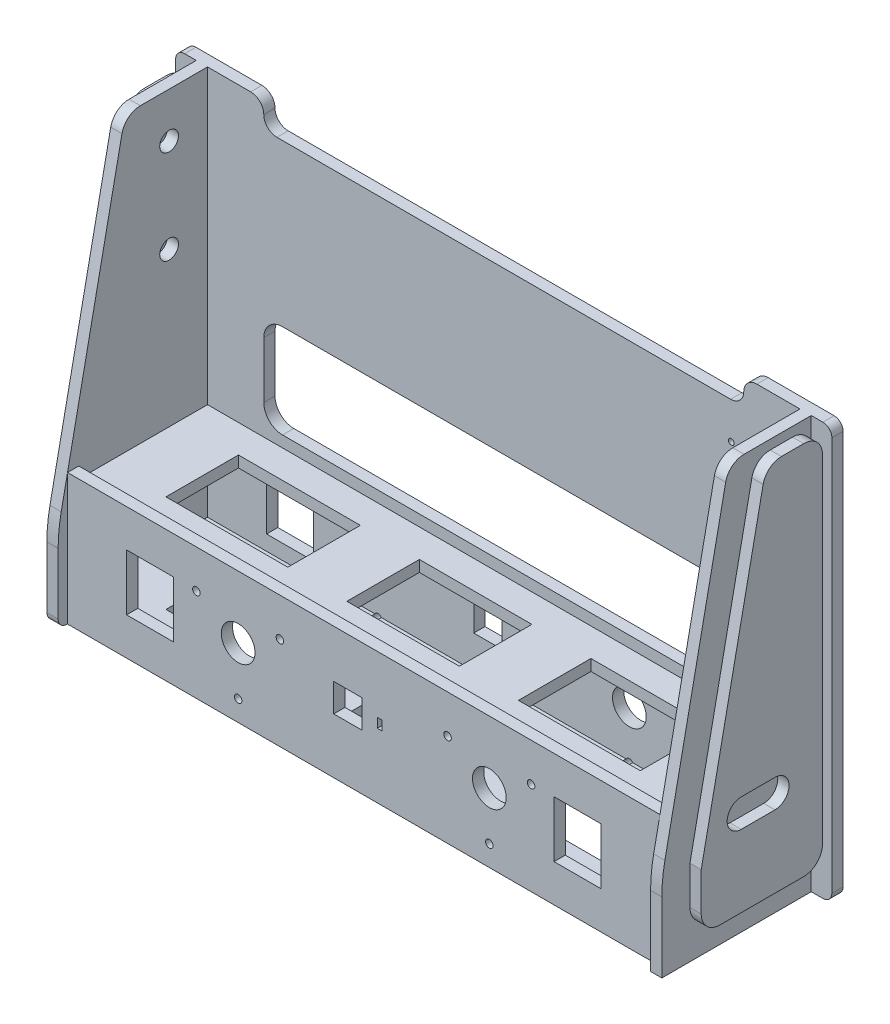
SolidWorks part; units mm, degrees
material "Birch plywood FK"
ref_plane "Спереди" through (0, 0, 0) normal (0, 0, 1) x (1, 0, 0)
ref_plane "Сверху" through (0, 0, 0) normal (0, 1, 0) x (1, 0, 0)
ref_plane "Справа" through (0, 0, 0) normal (1, 0, 0) x (0, 0, -1)
sketch "Эскиз1" plane through (0, 0, 0) normal (1, 0, 0) x (0, 0, -1)
  line L0 (0, 220) -> (0, 0)
  line L1 (0, 0) -> (-95, 0)
  line L2 (-95, 0) -> (-50, 220)
  line L3 (-50, 220) -> (0, 220)
  dimension "D1" = 220
  dimension "D2" = 95
  dimension "D3" = 50
extrude "Бобышка-Вытянуть1" add sketch "Эскиз1" along normal blind 340
sketch "Эскиз2" plane through (0, 220, 0) normal (0, 1, 0) x (1, 0, 0)
  line L0 (170, -95) -> (170, 0) construction
  line L1 (340, -95) -> (0, -95) construction
  line L2 (340, 0) -> (0, 0) construction
  line L3 (340, -50) -> (340, -95) construction
  line L4 (12, -95) -> (328, -95)
  line L5 (12, -95) -> (12, -6)
  line L6 (12, -6) -> (328, -6)
  line L7 (328, -95) -> (328, -6)
  line L8 (12, -95) -> (328, -6) construction
  line L9 (12, -6) -> (328, -95) construction
  point P6 (170, -50.5)
  dimension "D1" = 12
  dimension "D2" = 6
extrude "Вырез-Вытянуть1" cut sketch "Эскиз2" against normal offset from surface (150 mm away) 70 up to face at (170, 0, 47.5)
sketch "Эскиз3" plane through (0, 70, 0) normal (0, 1, 0) x (1, 0, 0)
  line L0 (340, -95) -> (0, -95) construction
  line L1 (12, -80.6818) -> (328, -80.6818)
  line L2 (12, -80.6818) -> (12, -95)
  line L3 (12, -95) -> (328, -95)
  line L4 (328, -80.6818) -> (328, -95)
extrude "Вырез-Вытянуть2" cut sketch "Эскиз3" against normal through all
sketch "Эскиз4" plane through (0, 0, 80.6818) normal (0, 0, 1) x (1, 0, 0)
  line L0 (170, 70) -> (170, 0) construction
  line L1 (12, 70) -> (328, 70) construction
  line L2 (328, 0) -> (12, 0) construction
  line L3 (12, 0) -> (12, 70) construction
  line L4 (328, 12) -> (12, 12)
  line L5 (328, 12) -> (328, 58)
  line L6 (328, 58) -> (12, 58)
  line L7 (12, 12) -> (12, 58)
  line L8 (328, 12) -> (12, 58) construction
  line L9 (328, 58) -> (12, 12) construction
  line L10 (12, 70) -> (328, 70) construction
  line L12 (328, 64) -> (12, 64)
  line L13 (328, 64) -> (328, 70)
  line L14 (328, 70) -> (12, 70)
  line L15 (12, 64) -> (12, 70)
  line L16 (328, 64) -> (12, 70) construction
  line L17 (328, 70) -> (12, 64) construction
  line L18 (328, 6) -> (12, 6)
  line L19 (328, 6) -> (328, 0)
  line L20 (328, 0) -> (12, 0)
  line L21 (12, 6) -> (12, 0)
  line L22 (328, 6) -> (12, 0) construction
  line L23 (328, 0) -> (12, 6) construction
  point P6 (170, 35)
  point P15 (170, 67)
  point P21 (170, 3)
  dimension "D1" = 12
  dimension "D2" = 6
extrude "Вырез-Вытянуть3" cut sketch "Эскиз4" against normal offset from surface (68.6818 mm away) 6 from offset 6 up to face at (170, 110, 0) offset against normal yes
sketch "Эскиз5" plane through (0, 0, 6) normal (0, 0, 1) x (1, 0, 0)
  line L0 (170, 220) -> (170, 70) construction
  line L1 (328, 220) -> (12, 220) construction
  line L2 (12, 70) -> (328, 70) construction
  line L3 (12, 64) -> (12, 220) construction
  line L4 (298, 70) -> (42, 70)
  line L5 (298, 70) -> (298, 120)
  line L6 (298, 120) -> (42, 120)
  line L7 (42, 70) -> (42, 120)
  line L8 (298, 70) -> (42, 120) construction
  line L9 (298, 120) -> (42, 70) construction
  point P6 (170, 95)
  dimension "D1" = 30
  dimension "D2" = 50
extrude "Вырез-Вытянуть4" cut sketch "Эскиз5" against normal through all
sketch "Эскиз6" plane through (0, 70, 0) normal (0, 1, 0) x (1, 0, 0)
  line L0 (170, 0) -> (170, -80.6818) construction
  line L1 (42, 0) -> (298, 0) construction
  line L2 (12, -80.6818) -> (328, -80.6818) construction
  line L3 (12, -6) -> (42, -6) construction
  line L4 (140, -40.3409) -> (12, -40.3409) construction
  line L5 (12, -6) -> (12, -74.6818) construction
  line L6 (200, -59.6818) -> (140, -59.6818)
  line L7 (200, -59.6818) -> (200, -21)
  line L8 (200, -21) -> (140, -21)
  line L9 (140, -59.6818) -> (140, -21)
  line L10 (200, -59.6818) -> (140, -21) construction
  line L11 (200, -21) -> (140, -59.6818) construction
  line L13 (108.5, -21) -> (43.5, -21)
  line L14 (328, -6) -> (328, -74.6818) construction
  line L15 (328, -40.3409) -> (200, -40.3409) construction
  line L16 (108.5, -21) -> (108.5, -59.6818)
  line L17 (108.5, -59.6818) -> (43.5, -59.6818)
  line L19 (43.5, -21) -> (43.5, -59.6818)
  line L20 (108.5, -21) -> (43.5, -59.6818) construction
  line L21 (108.5, -59.6818) -> (43.5, -21) construction
  line L22 (296.5, -21) -> (231.5, -21)
  line L23 (296.5, -21) -> (296.5, -59.6818)
  line L24 (296.5, -59.6818) -> (231.5, -59.6818)
  line L25 (231.5, -21) -> (231.5, -59.6818)
  line L26 (296.5, -21) -> (231.5, -59.6818) construction
  line L27 (296.5, -59.6818) -> (231.5, -21) construction
  point P6 (170, -40.3409)
  point P18 (76, -40.3409)
  point P28 (264, -40.3409)
  dimension "D1" = 15
  dimension "D2" = 60
  dimension "D3" = 65
extrude "Вырез-Вытянуть5" cut sketch "Эскиз6" against normal through all
sketch "Эскиз8" plane through (0, 0, 0) normal (-1, 0, 0) x (0, 0, 1)
  line L0 (95, 0) -> (0, 0) construction
  line L1 (85.6818, 70) -> (95, 70)
  line L2 (85.6818, 70) -> (85.6818, 0)
  line L3 (85.6818, 0) -> (95, 0)
  line L4 (95, 70) -> (95, 0)
  line L5 (80.6818, 0) -> (80.6818, 70) construction
  line L6 (80.6818, 70) -> (74.6818, 70) construction
  dimension "D1" = 5
extrude "Вырез-Вытянуть7" cut sketch "Эскиз8" against normal through all
sketch "Эскиз10" plane through (0, 220, 0) normal (0, 1, 0) x (1, 0, 0)
  line L0 (328, -6) -> (12, -6) construction
  line L1 (0, 0) -> (-5, 0)
  line L2 (0, 0) -> (0, -6)
  line L3 (0, -6) -> (-5, -6)
  line L4 (-5, 0) -> (-5, -6)
  line L5 (340, 0) -> (345, 0)
  line L6 (340, 0) -> (340, -6)
  line L7 (340, -6) -> (345, -6)
  line L8 (345, 0) -> (345, -6)
  dimension "D1" = 5
  dimension "D2" = 5
extrude "Бобышка-Вытянуть3" add sketch "Эскиз10" against normal up to surface (220 mm away) up to face at (170, 0, 63.0114)
sketch "Эскиз12" plane through (0, 0, 0) normal (-1, 0, 0) x (0, 0, 1)
  circle A0 centre (26.5, 196) radius 5
  circle A1 centre (26.5, 146) radius 5
  dimension "D1" = 10
extrude "Вырез-Вытянуть9" cut sketch "Эскиз12" against normal offset from surface (328 mm away) 6 from offset 6 up to face at (340, 75.1111, 50.2409) offset against normal yes
sketch "Эскиз13" plane through (0, 0, 6) normal (0, 0, 1) x (1, 0, 0)
  line L0 (334, 191) -> (345, 191) construction
  line L1 (345, 0) -> (345, 220) construction
  line L2 (306.85, 191) -> (306.85, 151) construction
  line L3 (334, 151) -> (345, 151) construction
  line L4 (306.85, 171) -> (345, 171) construction
  line L5 (340, 220) -> (340, 45.5556) construction
  circle A0 centre (306.85, 171) radius 16.4
  circle A2 centre (291.35, 186.5) radius 1.5
  circle A3 centre (322.35, 186.5) radius 1.5
  circle A4 centre (322.35, 155.5) radius 1.5
  circle A5 centre (291.35, 155.5) radius 1.5
  circle A6 centre (306.85, 171) radius 16.4 construction
  point P0 (306.85, 171)
  point P2 (0, 0)
  dimension "D1" = 3
  dimension "D2" = 33.15
extrude "Вырез-Вытянуть10" cut sketch "Эскиз13" against normal through all
fillet "Скругление2" radius 10 2 edges at (6, 220, 50) (334, 220, 50)
fillet "Скругление4" radius 80 2 edges at (334, 45.5556, 85.6818) (6, 45.5556, 85.6818)
sketch "Эскиз16" plane through (0, 0, 80.6818) normal (0, 0, 1) x (1, 0, 0)
  circle A0 centre (103, 36.7238) radius 9
  circle A1 centre (237, 36.7238) radius 9
  dimension "D1" = 18
extrude "Вырез-Вытянуть12" cut sketch "Эскиз16" against normal through all
sketch "Эскиз19" plane through (0, 0, 80.6818) normal (0, 0, 1) x (1, 0, 0)
  line L0 (161.5, 37) -> (178.5, 37) construction
  line L1 (169, 29.5) -> (154, 29.5)
  line L2 (169, 29.5) -> (169, 44.5)
  line L3 (169, 44.5) -> (154, 44.5)
  line L4 (154, 29.5) -> (154, 44.5)
  line L5 (169, 29.5) -> (154, 44.5) construction
  line L6 (169, 44.5) -> (154, 29.5) construction
  line L7 (179.75, 34.5) -> (177.25, 34.5)
  line L8 (179.75, 34.5) -> (179.75, 39.5)
  line L9 (179.75, 39.5) -> (177.25, 39.5)
  line L10 (177.25, 34.5) -> (177.25, 39.5)
  line L11 (179.75, 34.5) -> (177.25, 39.5) construction
  line L12 (179.75, 39.5) -> (177.25, 34.5) construction
  line L13 (170, 37) -> (170, -29) construction
  line L14 (153.0926, -29) -> (186.9074, -29) construction
  line L15 (60, 24.5) -> (280, 24.5) construction
  circle A0 centre (125.2775, 49.5857) radius 2
  circle A1 centre (80.7225, 49.5857) radius 2
  circle A2 centre (103, 11) radius 2
  circle A3 centre (214.7225, 49.5857) radius 2
  circle A4 centre (259.2775, 49.5857) radius 2
  circle A5 centre (237, 11) radius 2
  point P0 (161.5, 37)
  point P5 (178.5, 37)
  dimension "D7" = 4
  dimension "D1" = 5
  dimension "D2" = 2.5
  dimension "D3" = 12.5
  dimension "D4" = 17
  dimension "D5" = 15
  dimension "D6" = 15
extrude "Вырез-Вытянуть15" cut sketch "Эскиз19" against normal through all
fillet "Скругление5" radius 4.8 5 edges at (-5, 220, 3) (6, 0, 85.6818) (-5, 0, 3) (345, 0, 3) (345, 220, 3)
fillet "Скругление6" radius 10 4 edges at (298, 70, 3) (298, 120, 3) (42, 70, 3) (42, 120, 3)
sketch "Эскиз20" plane through (0, 0, 6) normal (0, 0, 1) x (1, 0, 0)
  line L0 (319.5142, 124.6) -> (309.5142, 124.6) construction
  line L1 (319.5142, 124.1) -> (309.5142, 124.1)
  line L2 (319.5142, 125.1) -> (309.5142, 125.1)
  line L3 (319.5142, 115.1) -> (309.5142, 115.1) construction
  line L4 (319.5142, 114.6) -> (309.5142, 114.6)
  line L5 (319.5142, 115.6) -> (309.5142, 115.6)
  arc A0 (319.5142, 124.1) -> (319.5142, 125.1) centre (319.5142, 124.6) ccw
  arc A1 (309.5142, 125.1) -> (309.5142, 124.1) centre (309.5142, 124.6) ccw
  arc A2 (319.5142, 114.6) -> (319.5142, 115.6) centre (319.5142, 115.1) ccw
  arc A3 (309.5142, 115.6) -> (309.5142, 114.6) centre (309.5142, 115.1) ccw
  point P2 (314.5142, 124.6)
  point P7 (314.5142, 115.1)
  dimension "D1" = 1
  dimension "D2" = 10
extrude "Вырез-Вытянуть16" cut sketch "Эскиз20" against normal through all
sketch "Эскиз21" plane through (0, 0, 6) normal (0, 0, 1) x (1, 0, 0)
  line L0 (170, 220) -> (170, 0) construction
  line L1 (328, 220) -> (12, 220) construction
  line L2 (328, 0) -> (12, 0) construction
  line L3 (12, 70) -> (12, 212.004) construction
  line L4 (298, 206) -> (42, 206)
  line L5 (298, 206) -> (298, 220)
  line L6 (298, 220) -> (42, 220)
  line L7 (42, 206) -> (42, 220)
  line L8 (298, 206) -> (42, 220) construction
  line L9 (298, 220) -> (42, 206) construction
  line L10 (120.214, 209) -> (154.0288, 209) construction
  point P6 (170, 213)
  dimension "D1" = 30
  dimension "D2" = 3
extrude "Вырез-Вытянуть17" cut sketch "Эскиз21" against normal through all
fillet "Скругление7" radius 7 4 edges at (298, 206, 3) (298, 220, 3) (42, 206, 3) (42, 220, 3)
ref_plane "Плоскость1" through (170, 0, 0) normal (-1, 0, 0) x (0, 0, 1)
sketch "Эскиз22" plane through (0, 0, 0) normal (-1, 0, 0) x (0, 0, 1)
  line L0 (16, 215) -> (27.8611, 215)
  line L2 (37.6583, 207.004) -> (70.6818, 45.5556)
  line L3 (70.6818, 45.5556) -> (70.6818, 25)
  line L4 (60.6818, 15) -> (16, 15)
  line L5 (6, 220) -> (41.8384, 220) construction
  line L6 (51.6356, 212.004) -> (84.059, 53.4893) construction
  line L7 (80.8818, 0) -> (6, 0) construction
  line L8 (85.6818, 37.4576) -> (85.6818, 4.8) construction
  line L9 (6, 0) -> (6, 220) construction
  line L10 (6, 205) -> (6, 220)
  line L11 (6, 220) -> (50, 220)
  line L12 (50, 220) -> (85.6818, 45.5556)
  line L13 (85.6818, 45.5556) -> (85.6818, 0)
  line L14 (85.6818, 0) -> (6, 0)
  line L15 (6, 0) -> (6, 25)
  line L16 (49.3409, 61) -> (31.3409, 61) construction
  line L17 (49.3409, 53.5) -> (31.3409, 53.5)
  line L18 (49.3409, 68.5) -> (31.3409, 68.5)
  line L19 (40.3409, 64) -> (40.3409, 58) construction
  line L20 (6, 64) -> (74.6818, 64) construction
  line L21 (6, 58) -> (74.6818, 58) construction
  arc A0 (70.6818, 25) -> (60.6818, 15) centre (60.6818, 25) cw
  arc A1 (27.8611, 215) -> (37.6583, 207.004) centre (27.8611, 205) cw
  arc A2 (16, 215) -> (6, 205) centre (16, 205) ccw
  arc A3 (6, 25) -> (16, 15) centre (16, 25) ccw
  arc A4 (49.3409, 53.5) -> (49.3409, 68.5) centre (49.3409, 61) ccw
  arc A5 (31.3409, 68.5) -> (31.3409, 53.5) centre (31.3409, 61) ccw
  point P34 (40.3409, 61)
  dimension "D1" = 10
  dimension "D5" = 20
  dimension "D2" = 5
  dimension "D3" = 15
  dimension "D4" = 15
  dimension "D6" = 15
  dimension "D7" = 18
extrude "Вырез-Вытянуть18" cut sketch "Эскиз22" against normal blind 6
mirror "Зеркальное отражение1" about plane through (170, 0, 0) normal (-1, 0, 0) of "Вырез-Вытянуть18"
sketch "Эскиз23" plane through (0, 0, 80.6818) normal (0, 0, 1) x (1, 0, 0)
  line L0 (170, 70) -> (170, 0) construction
  line L1 (12, 70) -> (328, 70) construction
  line L2 (328, 0) -> (12, 0) construction
  line L3 (271.5, 50) -> (296.5, 20) construction
  line L4 (12, 0) -> (12, 70) construction
  line L5 (12, 35) -> (170, 35) construction
  line L6 (170, 35) -> (328, 35) construction
  line L7 (328, 0) -> (328, 70) construction
  line L8 (68.5, 20) -> (43.5, 20)
  line L9 (68.5, 20) -> (68.5, 50)
  line L10 (68.5, 50) -> (43.5, 50)
  line L11 (43.5, 20) -> (43.5, 50)
  line L12 (68.5, 20) -> (43.5, 50) construction
  line L13 (68.5, 50) -> (43.5, 20) construction
  line L14 (271.5, 20) -> (296.5, 50) construction
  line L15 (296.5, 20) -> (296.5, 50)
  line L16 (271.5, 50) -> (296.5, 50)
  line L17 (271.5, 20) -> (271.5, 50)
  line L18 (271.5, 20) -> (296.5, 20)
  line L19 (43.5, 58) -> (43.5, 64) construction
  point P13 (56, 35)
  point P22 (284, 35)
  dimension "D1" = 30
  dimension "D2" = 25
extrude "Вырез-Вытянуть19" cut sketch "Эскиз23" against normal through all
